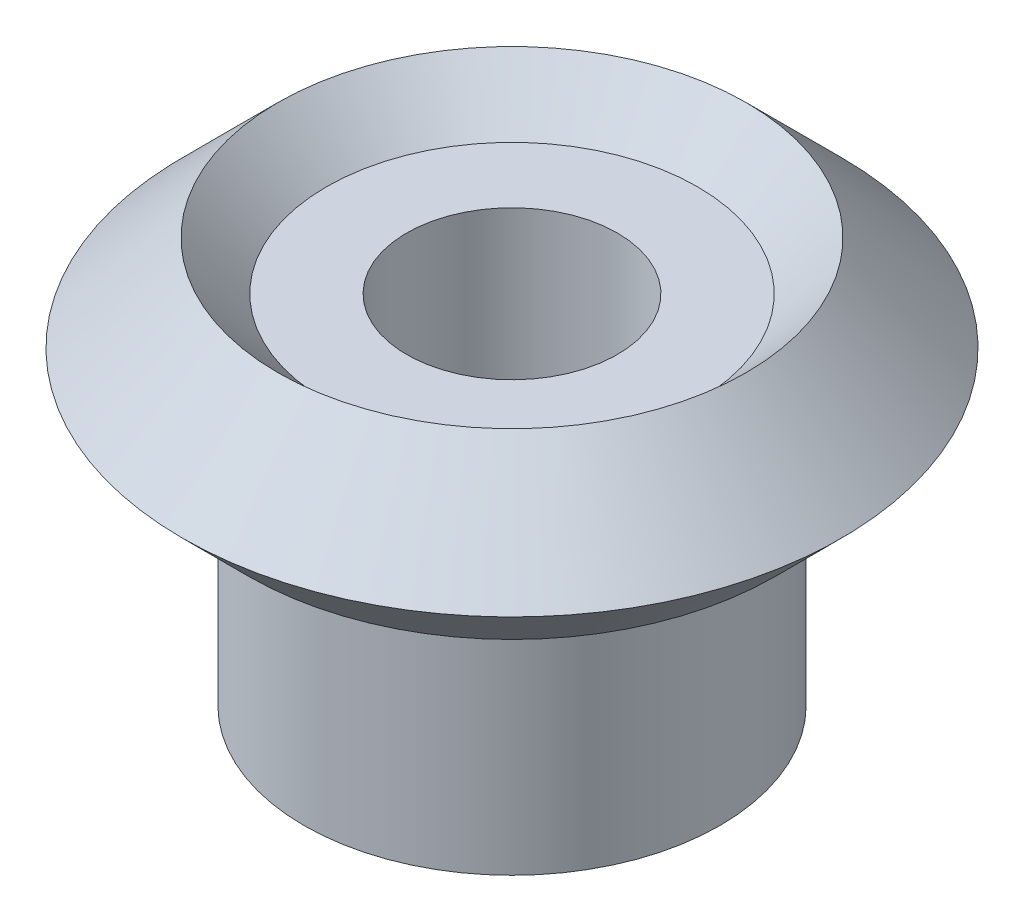
SolidWorks part; units mm, degrees
material "Brass"
ref_plane "Front Plane" through (0, 0, 0) normal (0, 0, 1) x (1, 0, 0)
ref_plane "Top Plane" through (0, 0, 0) normal (0, 1, 0) x (1, 0, 0)
ref_plane "Right Plane" through (0, 0, 0) normal (1, 0, 0) x (0, 0, -1)
sketch "Sketch1" plane through (0, 0, 0) normal (0, 0, 1) x (1, 0, 0)
  line L0 (0, 0) -> (0, 10843.806) construction
  line L1 (1.95, 0) -> (1.95, 6.6)
  line L2 (1.95, 6.6) -> (3.4322, 6.6)
  line L3 (3.4322, 6.6) -> (4.3322, 7.5)
  line L4 (4.3322, 7.5) -> (6.1, 5.7322)
  line L5 (6.1, 5.7322) -> (4.8678, 4.5)
  line L6 (3.85, 4.5) -> (3.85, 0)
  line L7 (3.85, 0) -> (1.95, 0)
  line L8 (4.8678, 4.5) -> (3.85, 4.5)
  dimension "D1" = 3.9
  dimension "D2" = 7.5
  dimension "D3" = 2.5
  dimension "D4" = 4.5
  dimension "D5" = 6.6
  dimension "D6" = 45
  dimension "D7" = 12.2
  dimension "D8" = 7.7
revolve "Revolve1" add sketch "Sketch1" angle 360 about L0
ref_axis "Axis1" through (0, 6.6, 0) along (0, -1, 0)
